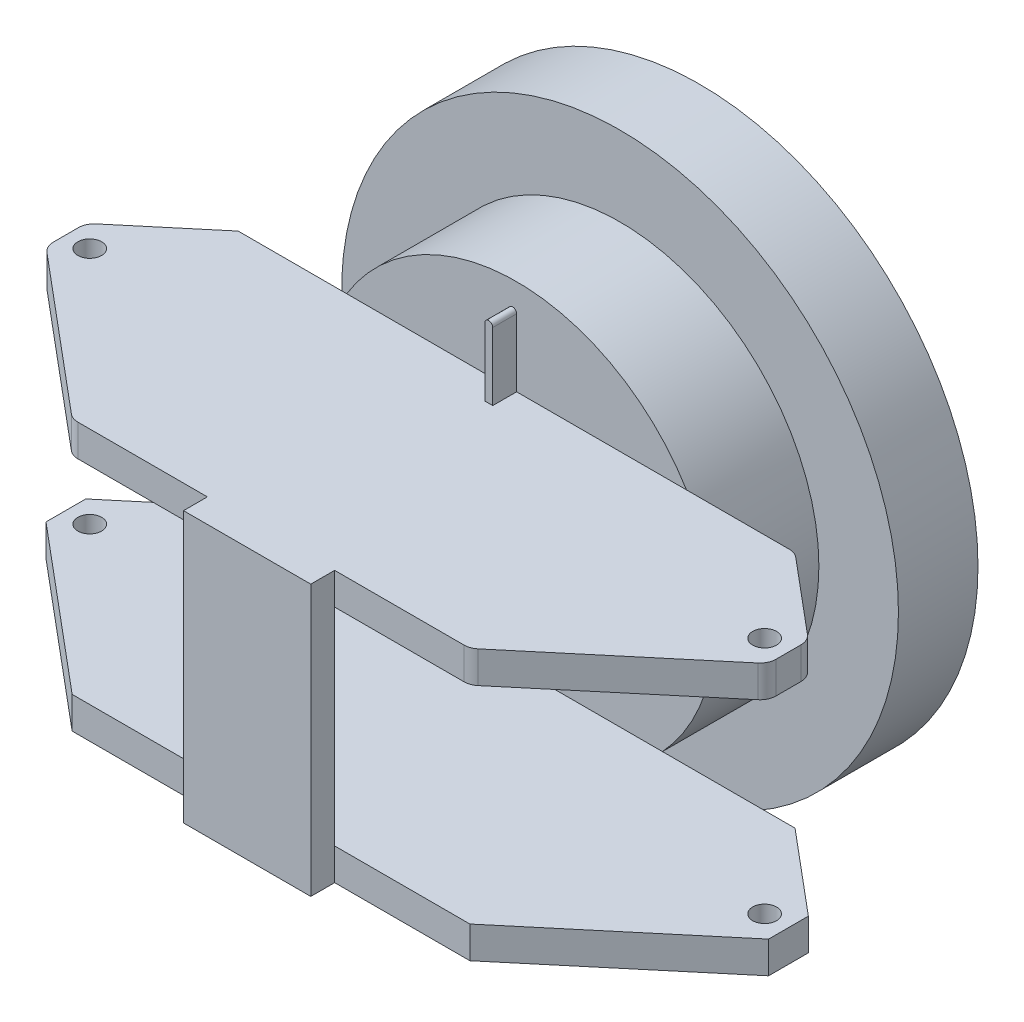
SolidWorks part; units mm, degrees
ref_plane "Front Plane" through (0, 0, 0) normal (0, 0, 1) x (1, 0, 0)
ref_plane "Top Plane" through (0, 0, 0) normal (0, 1, 0) x (1, 0, 0)
ref_plane "Right Plane" through (0, 0, 0) normal (1, 0, 0) x (0, 0, -1)
sketch "Sketch1" plane through (0, 0, 0) normal (0, 0, 1) x (1, 0, 0)
  circle A0 centre (0, 0) radius 35
  dimension "D1" = 70
extrude "Boss-Extrude1" add sketch "Sketch1" along normal blind 10
sketch "Sketch2" plane through (0, 0, 10) normal (0, 0, 1) x (1, 0, 0)
  circle A2 centre (0, 0) radius 25
  circle A3 centre (0, 0) radius 25
  dimension "D1" = 10
extrude "Boss-Extrude2" add sketch "Sketch2" along normal blind 13
ref_plane "Plane1" through (0, 13, 0) normal (0, 1, 0) x (1, 0, 0)
sketch "Sketch3" plane through (0, 13, 0) normal (0, 1, 0) x (1, 0, 0)
  line L0 (43.315, -23) -> (-43.315, -23)
  line L1 (-25, -23) -> (25, -23) construction
  line L2 (0, -23) -> (-35, -23)
  line L3 (-35, -23) -> (-45.4172, -31.7411)
  line L4 (-45.4172, -31.7411) -> (-45.4172, -36.7411)
  line L5 (-44.8082, -18.2717) -> (-45.4172, -17.6627)
  line L6 (-25, -23) -> (-25, -53.8731)
  line L7 (-25, -10) -> (-25, -23) construction
  line L8 (-45.4172, -36.7411) -> (-25, -53.8731)
  line L9 (-45.4172, -36.7411) -> (-45.4172, -46.9748)
  line L10 (-25, -53.8731) -> (25, -53.8731)
  line L11 (0, -53.8731) -> (0, -23)
  line L12 (25, -23) -> (25, -53.8731)
  line L13 (35, -23) -> (45.4172, -31.7411)
  line L14 (45.4172, -31.7411) -> (45.4172, -36.7411)
  line L15 (45.4172, -36.7411) -> (25, -53.8731)
  dimension "D1" = 35
  dimension "D2" = 40
  dimension "D3" = 5
  dimension "D4" = 50
  dimension "D5" = 26.6528
extrude "Boss-Extrude3" add sketch "Sketch3" against normal blind 4 contours L12 L0 L11 L10 | L10 L11 L0 L6 | L4 L8 L6 L2 L3 | L15 L14 L13 L0 L12 region at (33.0086, 13, 35.6779) region at (12.5, 13, 38.4366) region at (-12.5, 13, 38.4366) region at (-33.0086, 13, 35.6779)
fillet "Fillet1" radius 2 7 edges at (35, 11, 23) (45.4172, 11, 31.7411) (45.4172, 11, 36.7411) (25, 11, 53.8731) (-25, 11, 53.8731) (-45.4172, 11, 36.7411) (-45.4172, 11, 31.7411)
sketch "Sketch4" plane through (0, 13, 0) normal (0, 1, 0) x (1, 0, 0)
  line L0 (-45.4172, -34.2411) -> (-42.4172, -34.2411)
  line L1 (-45.4172, -32.6737) -> (-45.4172, -35.8085) construction
  circle A0 centre (-42.4172, -34.2411) radius 1.5
  dimension "D2" = 3
  dimension "D1" = 3
extrude "Cut-Extrude1" cut sketch "Sketch4" against normal blind 4 contours A0 region at (-42.4172, 13, 35.6986)
ref_plane "Plane4" through (0, -4, 0) normal (0, -1, 0) x (-1, 0, 0)
mirror "Mirror1" about plane through (0, 0, 0) normal (1, 0, 0) of "Cut-Extrude1"
mirror "Mirror2" about plane through (0, -4, 0) normal (0, -1, 0) of "Mirror1", "Boss-Extrude3"
sketch "Sketch5" plane through (0, 0, 23) normal (0, 0, 1) x (1, 0, 0)
  line L0 (0, 25) -> (0, 13) construction
  line L1 (28.5008, 13) -> (-28.5008, 13) construction
  line L2 (0, 13) -> (-1, 13)
  line L3 (-1, 13) -> (-1, 22)
  line L4 (-1, 22) -> (0, 22)
  arc A0 (21.3542, 13) -> (-21.3542, 13) centre (0, 0) ccw construction
  line M2 (-21.3542, 13) -> (21.3542, 13)
  dimension "D1" = 1
  dimension "D2" = 9
extrude "Boss-Extrude4" add sketch "Sketch5" along normal blind 3 contours L0 L4 L3 M2 region at (-0.5, 17.5, 23)
fillet "Fillet2" 2 edges at (-1, 22, 24.5) (0, 22, 24.5) type full round first side face at (-1, 17.5, 24.5) second side face at (0, 17.5, 24.5) middle face at (-0.5, 22, 24.5)
mirror "Mirror3" about plane through (0, -4, 0) normal (0, -1, 0) of "Fillet2", "Boss-Extrude4"
ref_plane "Plane2" through (0, 0, 53.8731) normal (0, 0, 1) x (1, 0, 0)
sketch "Sketch6" plane through (0, 0, 53.8731) normal (0, 0, 1) x (1, 0, 0)
  line L0 (-25, -21) -> (25, -21) construction
  line L1 (8, 21) -> (-8, 21)
  line L2 (8, 21) -> (8, -21)
  line L3 (8, -21) -> (-8, -21)
  line L4 (-8, 21) -> (-8, -21)
  line L5 (8, 21) -> (-8, -21) construction
  line L6 (8, -21) -> (-8, 21) construction
  point P0 (0, 0)
  dimension "D1" = 16
extrude "Boss-Extrude5" add sketch "Sketch6" along normal blind 3
sketch "Sketch7" plane through (0, 0, 0) normal (0, 0, -1) x (-1, 0, 0)
  circle A0 centre (0, 0) radius 10
  dimension "D1" = 20
extrude "Cut-Extrude2" cut sketch "Sketch7" against normal blind 10
ref_plane "Plane3" through (0, 0, 0) normal (0, 1, 0) x (1, 0, 0)
sketch "Sketch9" plane through (0, 0, 56.8731) normal (0, 0, 1) x (1, 0, 0)
  line L0 (-8, 21) -> (8, 21)
  line L1 (-8, 21) -> (-8, -21) construction
  line L2 (8, -21) -> (8, 21) construction
  line L3 (8, 21) -> (8, 13)
  line L4 (28.5008, 13) -> (-28.5008, 13) construction
  line L5 (8, 13) -> (-8, 13)
  line L6 (-8, 13) -> (-8, 21)
  line L7 (8, 21) -> (-8, 21) construction
extrude "Cut-Extrude4" cut sketch "Sketch9" against normal blind 10
